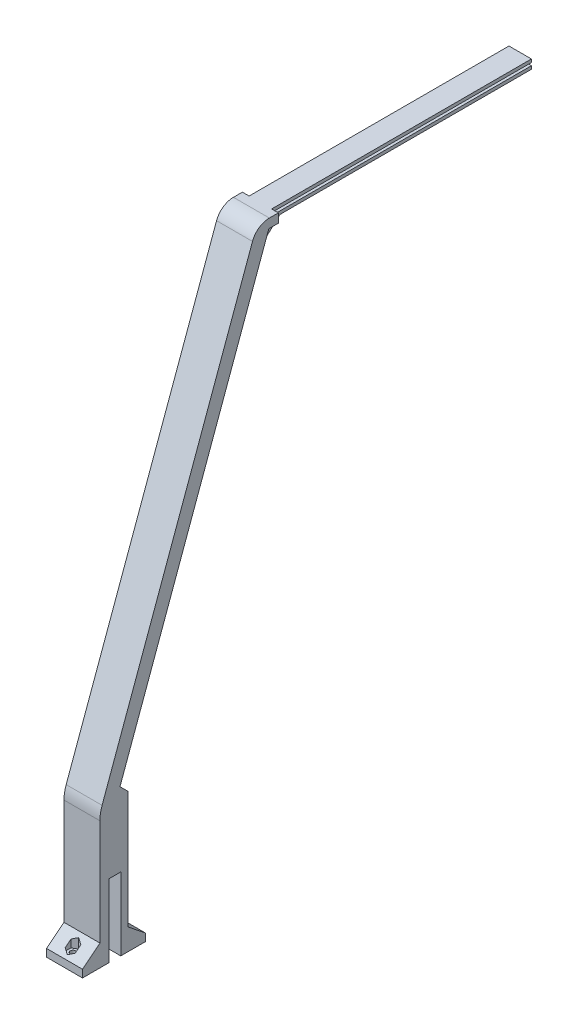
SolidWorks part; units mm, degrees
ref_plane "Front Plane" through (0, 0, 0) normal (0, 0, 1) x (1, 0, 0)
ref_plane "Top Plane" through (0, 0, 0) normal (0, 1, 0) x (1, 0, 0)
ref_plane "Right Plane" through (0, 0, 0) normal (1, 0, 0) x (0, 0, -1)
sketch "Sketch2" plane through (0, 0, 0) normal (1, 0, 0) x (0, 0, -1)
  line L0 (36.0729, 122.5) -> (-51.2799, -117.5)
  line L1 (-51.2799, -117.5) -> (-51.2799, -192)
  line L5 (-42.7665, -117.5) -> (42.7665, 117.5)
  line L6 (192.7665, 122.5) -> (36.0729, 122.5)
  line L7 (-42.7665, -117.5) -> (-35.6799, -117.5)
  line L9 (-39.6799, -151.5) -> (-46.2799, -151.5)
  line L10 (-46.2799, -151.5) -> (-46.2799, -192)
  line L13 (-35.6799, -117.5) -> (-35.6799, -192)
  line L14 (-35.6799, -192) -> (-39.6799, -192)
  line L15 (-39.6799, -192) -> (-39.6799, -151.5)
  line L16 (-51.2799, -192) -> (-46.2799, -192)
  line L18 (192.7665, 122.5) -> (192.7665, 117.5)
  line L19 (192.7665, 117.5) -> (42.7665, 117.5)
  point P12 (0, 0)
  dimension "D1" = 34
  dimension "D2" = 4
  dimension "D3" = 5
  dimension "D4" = 6.6
  dimension "D5" = 150
  dimension "D6" = 5
  dimension "D7" = 40.5
  dimension "D9" = 240
  dimension "D10" = 8
  dimension "D11" = 70
extrude "Boss-Extrude1" add sketch "Sketch2" along normal mid plane 20
chamfer "Chamfer1" distance 10 angle 45 1 edges at (0, -117.5, 42.7665) first distance on face at (0, -117.5, 39.2232)
sketch "Sketch6" plane through (10, 0, 0) normal (1, 0, 0) x (0, 0, -1)
  line L0 (-51.2799, -180) -> (-66.2799, -192)
  line L1 (-66.2799, -192) -> (-51.2799, -192)
  line L2 (-51.2799, -192) -> (-51.2799, -180)
  line L3 (-51.2799, -117.5) -> (-51.2799, -192) construction
  line L4 (-35.6799, -192) -> (-20.6799, -192)
  line L5 (-20.6799, -192) -> (-35.6799, -180)
  line L6 (-35.6799, -192) -> (-35.6799, -114.5866) construction
  line L7 (-35.6799, -180) -> (-35.6799, -192)
  point P12 (0, 0)
  dimension "D1" = 15
  dimension "D2" = 12
extrude "Boss-Extrude2" add sketch "Sketch6" against normal up to vertex (20 mm away) up to point (-10, -192, 51.2799)
sketch "Sketch7" plane through (0, -192, 0) normal (0, -1, 0) x (-1, 0, 0)
  line L0 (0, -66.2799) -> (0, -46.2799) construction
  line L1 (10, -66.2799) -> (-10, -66.2799) construction
  line L2 (-10, -46.2799) -> (10, -46.2799) construction
  line L3 (0, -20.6799) -> (0, -39.6799) construction
  line L4 (10, -20.6799) -> (-10, -20.6799) construction
  line L5 (-10, -39.6799) -> (10, -39.6799) construction
  circle A0 centre (0, -56.2799) radius 1.5
  circle A1 centre (0, -30.1799) radius 1.5
  dimension "D1" = 3
  dimension "D2" = 3
extrude "Cut-Extrude1" cut sketch "Sketch7" against normal blind 20
ref_plane "Plane1" through (0, -187, 0) normal (0, -1, 0) x (-1, 0, 0)
sketch "Sketch9" plane through (0, -187, 0) normal (0, -1, 0) x (-1, 0, 0)
  line L1 (2.75, -57.8676) -> (2.75, -54.6922)
  line L2 (2.75, -54.6922) -> (0, -53.1045)
  line L3 (0, -53.1045) -> (-2.75, -54.6922)
  line L4 (-2.75, -54.6922) -> (-2.75, -57.8676)
  line L5 (-2.75, -57.8676) -> (0, -59.4554)
  line L6 (0, -59.4554) -> (2.75, -57.8676)
  line L7 (2.75, -31.7676) -> (2.75, -28.5922)
  line L8 (2.75, -28.5922) -> (0, -27.0045)
  line L9 (0, -27.0045) -> (-2.75, -28.5922)
  line L10 (-2.75, -28.5922) -> (-2.75, -31.7676)
  line L11 (-2.75, -31.7676) -> (0, -33.3554)
  line L12 (0, -33.3554) -> (2.75, -31.7676)
  circle A0 centre (0, -56.2799) radius 2.75 construction
  circle A1 centre (0, -30.1799) radius 2.75 construction
  point P10 (0, 0)
  point P19 (0, -29.634)
  point P21 (0, 0)
  point P22 (0, -29.634)
  dimension "D1" = 5.5
  dimension "D2" = 5.5
extrude "Cut-Extrude3" cut sketch "Sketch9" against normal blind 20
fillet "Fillet5" radius 20 1 edges at (0, -117.5, 51.2799)
fillet "Fillet6" radius 10 1 edges at (0, 122.5, -36.0729)
sketch "Sketch10" plane through (10, 0, 0) normal (1, 0, 0) x (0, 0, -1)
  line L0 (-51.2799, -180) -> (-66.2799, -192) construction
  line L1 (-66.2799, -192) -> (-60.9799, -192)
  line L2 (-66.2799, -192) -> (-66.2799, -187.76)
  line L3 (-66.2799, -187.76) -> (-60.9799, -187.76)
  line L4 (-60.9799, -192) -> (-60.9799, -187.76)
  line L6 (-43.4799, -150) -> (-43.4799, -190.5) construction
  line L8 (-25.9799, -192) -> (-25.9799, -187.76)
  line L9 (-20.6799, -187.76) -> (-25.9799, -187.76)
  line L10 (-20.6799, -192) -> (-20.6799, -187.76)
  line L11 (-20.6799, -192) -> (-25.9799, -192)
  point P13 (-20.5688, -190.5)
  point P14 (-20.134, -190.5)
  dimension "D1" = 35
extrude "Cut-Extrude4" cut sketch "Sketch10" against normal through all
sketch "Sketch11" plane through (0, 122.5, 0) normal (0, 1, 0) x (1, 0, 0)
  line L5 (-10, 43.075) -> (10, 43.075) construction
  line L6 (-10, 192.7665) -> (-6.25, 192.7665)
  line L7 (-10, 192.7665) -> (-10, 48.075)
  line L8 (-10, 48.075) -> (-6.25, 48.075)
  line L9 (-6.25, 192.7665) -> (-6.25, 48.075)
  line L10 (10, 192.7665) -> (6.25, 192.7665)
  line L11 (10, 192.7665) -> (10, 48.075)
  line L12 (10, 48.075) -> (6.25, 48.075)
  line L13 (6.25, 192.7665) -> (6.25, 48.075)
  dimension "D1" = 12.5
  dimension "D2" = 5
extrude "Cut-Extrude5" cut sketch "Sketch11" against normal through all
sketch "Sketch13" plane through (6.25, 0, 0) normal (1, 0, 0) x (0, 0, -1)
  line L0 (52.7665, 117.5) -> (37.7665, 103.7626)
  line L1 (192.7665, 117.5) -> (48.075, 117.5) construction
  line L2 (-40.098, -110.1685) -> (42.7665, 117.5) construction
  line L3 (37.7665, 103.7626) -> (42.7665, 117.5)
  line L4 (42.7665, 117.5) -> (52.7665, 117.5)
  dimension "D1" = 10
  dimension "D2" = 15
extrude "Boss-Extrude4" add sketch "Sketch13" against normal blind 12.5
sketch "Sketch12" plane through (0, 0, -192.7665) normal (0, 0, -1) x (-1, 0, 0)
  line L0 (-6.25, 117.5) -> (-6.25, 122.5) construction
  line L1 (-6.25, 120.75) -> (-4.25, 120.75)
  line L2 (-6.25, 120.75) -> (-6.25, 119.25)
  line L3 (-6.25, 119.25) -> (-4.25, 119.25)
  line L4 (-4.25, 120.75) -> (-4.25, 119.25)
  line L5 (0, 122.5) -> (0, 117.5) construction
  line L6 (-6.25, 122.5) -> (6.25, 122.5) construction
  line L7 (-6.25, 117.5) -> (6.25, 117.5) construction
  line L8 (4.25, 120.75) -> (4.25, 119.25)
  line L9 (6.25, 119.25) -> (4.25, 119.25)
  line L10 (6.25, 120.75) -> (6.25, 119.25)
  line L11 (6.25, 120.75) -> (4.25, 120.75)
  line L12 (-6.25, 122.5) -> (-6.25, 120.75) construction
  line L13 (-6.25, 117.5) -> (-6.25, 119.25) construction
  point P18 (-6.25, 122.5)
  dimension "D1" = 1.75
  dimension "D2" = 1.5
  dimension "D3" = 2
extrude "Cut-Extrude6" cut sketch "Sketch12" against normal up to vertex (144.6915 mm away) up to point (10, 122.5, -48.075)
